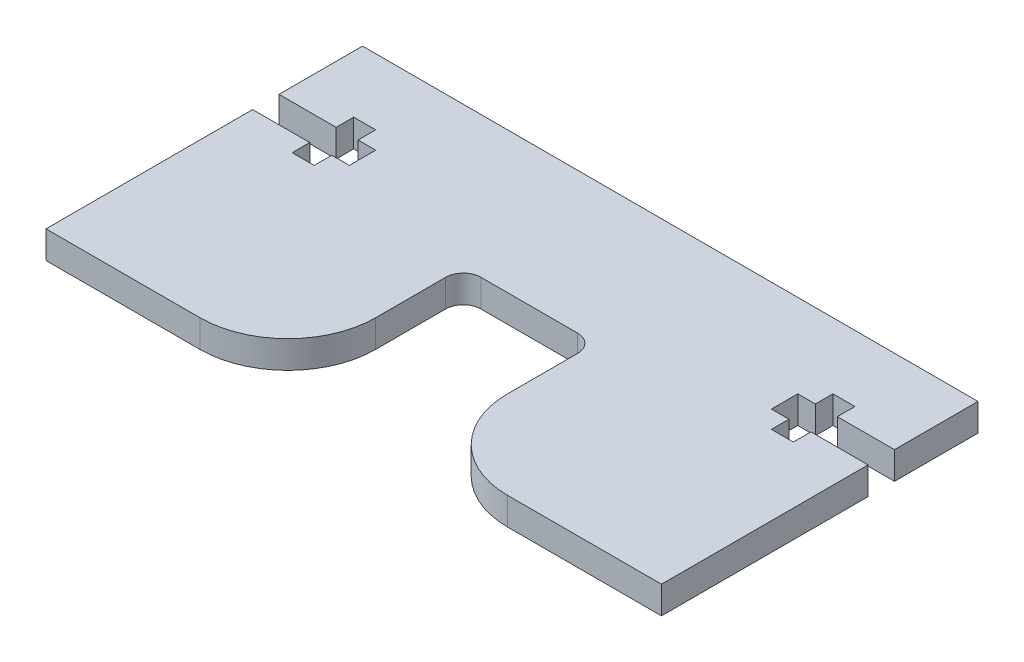
SolidWorks part; units mm, degrees
ref_plane "Front Plane" through (0, 0, 0) normal (0, 0, 1) x (1, 0, 0)
ref_plane "Top Plane" through (0, 0, 0) normal (0, 1, 0) x (1, 0, 0)
ref_plane "Right Plane" through (0, 0, 0) normal (1, 0, 0) x (0, 0, -1)
sketch "Sketch1" plane through (0, 0, 0) normal (0, 1, 0) x (1, 0, 0)
  line L0 (0, 25) -> (35, 25) construction
  line L1 (0, 36) -> (35, 36)
  line L2 (0, 36) -> (0, 0)
  line L3 (0, 0) -> (35, 0)
  line L4 (35, 36) -> (35, 26.5)
  line L5 (35, 26.5) -> (28.5, 26.5)
  line L6 (28.5, 26.5) -> (28.5, 28.5)
  line L7 (28.5, 28.5) -> (26, 28.5)
  line L8 (26, 28.5) -> (26, 26.5)
  line L9 (26, 26.5) -> (24, 26.5)
  line L10 (24, 26.5) -> (24, 23.5)
  line L11 (24, 23.5) -> (26, 23.5)
  line L12 (26, 23.5) -> (26, 21.5)
  line L13 (26, 21.5) -> (28.5, 21.5)
  line L14 (28.5, 21.5) -> (28.5, 23.5)
  line L15 (28.5, 23.5) -> (35, 23.5)
  line L16 (35, 23.5) -> (35, 0)
  point P17 (24, 25)
  dimension "D1" = 35
  dimension "D2" = 2.5
  dimension "D3" = 9
  dimension "D4" = 2
  dimension "D5" = 3
  dimension "D6" = 7.5
  dimension "D7" = 7
  dimension "D8" = 25
extrude "Boss-Extrude1" add sketch "Sketch1" along normal mid plane 3.125
mirror "Mirror1" about plane through (0, 0, 0) normal (1, 0, 0) of "Boss-Extrude1"
sketch "Sketch2" plane through (0, -1.5625, 0) normal (0, -1, 0) x (1, 0, 0)
  line L0 (-35, 0) -> (35, 0) construction
  line L1 (-7.5, 0) -> (7.5, 0)
  line L2 (-7.5, 0) -> (-7.5, -19.9625)
  line L3 (-7.5, -19.9625) -> (7.5, -19.9625)
  line L4 (7.5, 0) -> (7.5, -19.9625)
  line L5 (-7.5, 0) -> (7.5, -19.9625) construction
  line L6 (-7.5, -19.9625) -> (7.5, 0) construction
  line L7 (0, -9.9813) -> (0, 0) construction
  line L8 (-35, -9.9625) -> (35, -9.9625) construction
  point P4 (0, -9.9813)
  dimension "D1" = 15
  dimension "D2" = 10
extrude "Cut-Extrude1" cut sketch "Sketch2" against normal through all
fillet "Fillet1" radius 10 2 edges at (-7.5, 0, 0) (7.5, 0, 0)
fillet "Fillet2" radius 2 2 edges at (7.5, 0, -19.9625) (-7.5, 0, -19.9625)
